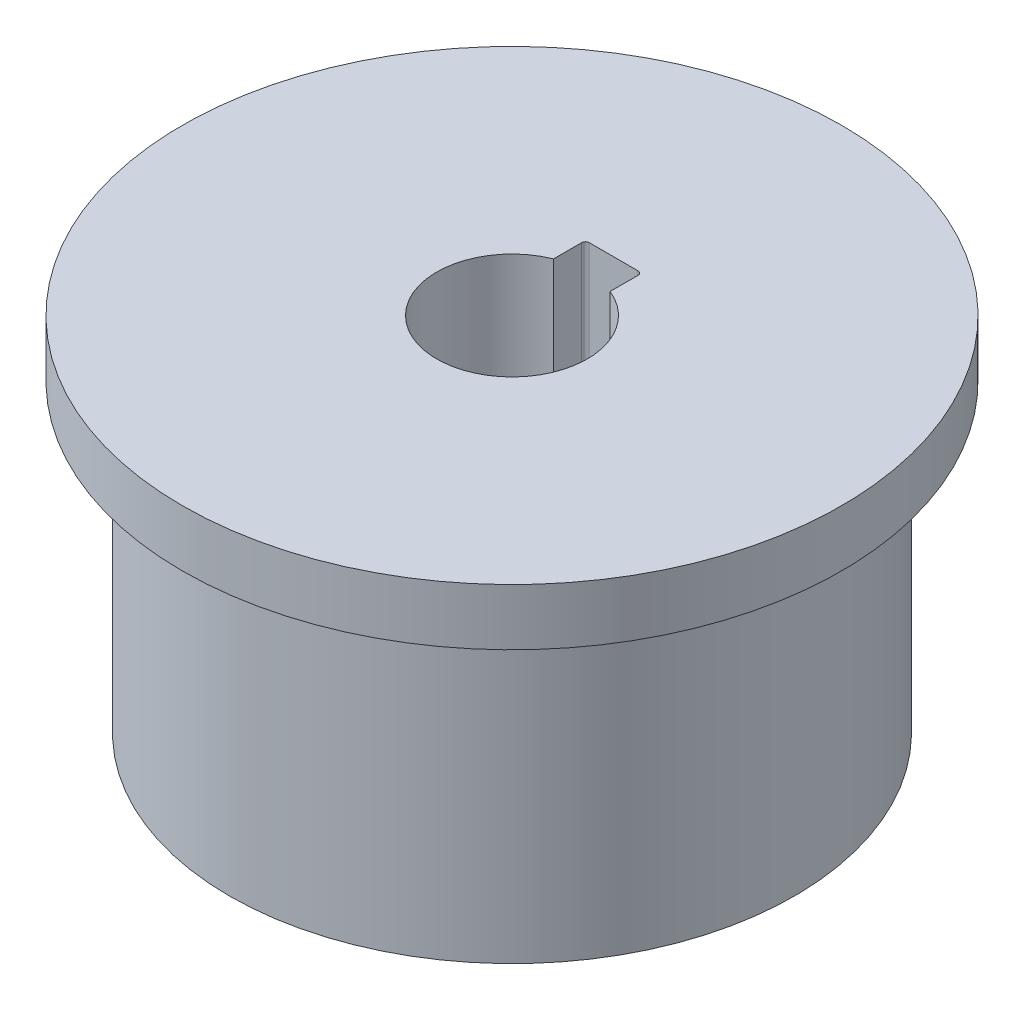
SolidWorks part; units mm, degrees
ref_plane "Plan de face" through (0, 0, 0) normal (0, 0, 1) x (1, 0, 0)
ref_plane "Plan de dessus" through (0, 0, 0) normal (0, 1, 0) x (1, 0, 0)
ref_plane "Plan de droite" through (0, 0, 0) normal (1, 0, 0) x (0, 0, -1)
sketch "Sketch1" plane through (0, 0, 0) normal (0, 0, 1) x (1, 0, 0)
  line L0 (0, 12.7093) -> (0, -8.2237) construction
  line L1 (4, 19.2) -> (17.5, 19.2)
  line L2 (17.5, 19.2) -> (17.5, 16.2)
  line L3 (17.5, 16.2) -> (15, 16.2)
  line L4 (15, 16.2) -> (15, 0)
  line L5 (15, 0) -> (6.4, 0)
  line L10 (2, 4) -> (2, -3)
  line L11 (2, -3) -> (3.4, -3)
  line L12 (3.4, -3) -> (6.4, 0)
  line L13 (2, 4) -> (4, 4)
  line L14 (4, 4) -> (4, 19.2)
  point P7 (5.4497, 19.2)
  point P15 (0, 0)
  dimension "D1" = 16.2
  dimension "D2" = 3
  dimension "D3" = 17.5
  dimension "D4" = 15
  dimension "D5" = 4
  dimension "D6" = 3
  dimension "D7" = 3.4
  dimension "D8" = 45
  dimension "D9" = 8
  dimension "D10" = 4
revolve "Revolve1" add sketch "Sketch1" angle 360 about L0
chamfer "Chanfrein1" distance 1 angle 45 1 edges at (0, 4, 2)
sketch "Esquisse1" plane through (0, 19.2, 0) normal (0, 1, 0) x (1, 0, 0)
  line L0 (-1.5, 3.7081) -> (-1.5, 5.4)
  line L1 (-1.5, 5.4) -> (1.5, 5.4)
  line L2 (1.5, 5.4) -> (1.5, 3.7081)
  circle A0 centre (0, 0) radius 4 construction
  arc A2 (-1.5, 3.7081) -> (1.5, 3.7081) centre (0, 0) cw
  point P4 (0, 5.4)
  circle M2 centre (0, 0) radius 4
  dimension "D1" = 1.4
  dimension "D2" = 3
extrude "Enlèv. mat.-Extru.1" cut sketch "Esquisse1" against normal up to surface (15.2 mm away) contours L2 L1 L0 M2 region at (0, 19.2, -4.6496) up to face at (0, 4, -3)
fillet "Congé1" radius 0.2 2 edges at (1.5, 11.6, -5.4) (-1.5, 11.6, -5.4)
